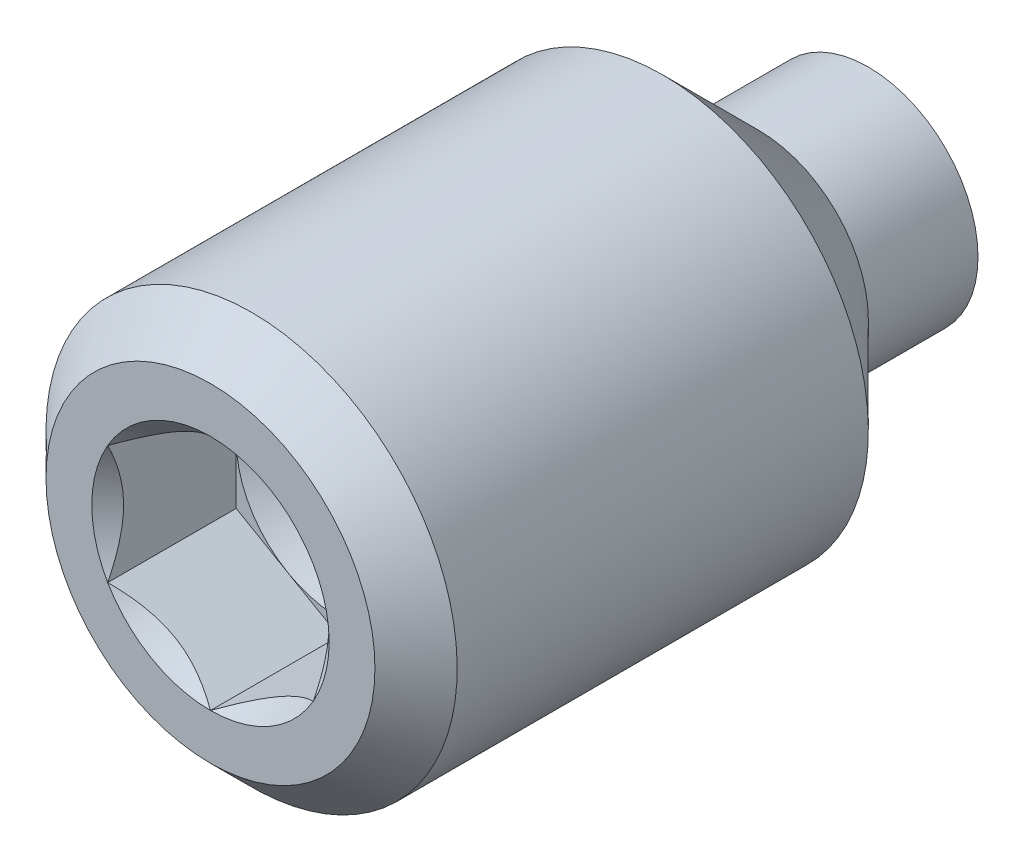
SolidWorks part; units mm, degrees
ref_plane "Front" through (0, 0, 0) normal (0, 0, 1) x (1, 0, 0)
ref_plane "Top" through (0, 0, 0) normal (0, 1, 0) x (1, 0, 0)
ref_plane "Right" through (0, 0, 0) normal (1, 0, 0) x (0, 0, -1)
sketch "Sketch22" plane through (0, 0, 0) normal (1, 0, 0) x (0, 0, -1)
  line L0 (-2.4, 0) -> (-2.4, 1.2)
  line L1 (-2.4, 1.2) -> (-2.1, 1.5)
  line L2 (-2.1, 1.5) -> (0.9, 1.5)
  line L3 (0.9, 1.5) -> (1.6, 0.8)
  line L5 (2.4, 0) -> (-2.4, 0)
  line L6 (2.4, 0) -> (1.6, 0) construction
  line L7 (1.6, 0) -> (1.6, 0.8) construction
  line L9 (-2.1, -1.5) -> (0.9, -1.5) construction
  line L10 (1.6, 0.8) -> (2.4, 0.8)
  line L11 (2.4, 0.8) -> (2.4, 0)
  line L12 (2.4, 0.8) -> (2.4, -0.8) construction
  dimension "Screw Dia" = 3
  dimension "Length" = 4
  dimension "D3" = 45
  dimension "D6" = 45
  dimension "D7" = 2.4
  dimension "A" = 1.6
  dimension "B" = 0.8
revolve "Revolve1" add sketch "Sketch22" angle 360 about L6
ref_plane "Plane2" through (0, 0, -1.6) normal (0, 0, 1) x (1, 0, 0)
sketch "Sketch27" plane through (0, 0, -1.6) normal (0, 0, 1) x (1, 0, 0)
  circle A0 centre (0, 0) radius 1.5
curve "Helix/Spiral1" pitch 0.5 height 4.5 turns 9
sketch "Sketch6" plane through (0, 0, 0) normal (1, 0, 0) x (0, 0, -1)
  line L0 (1.6938, 1.3376) -> (1.9438, 1.3376) construction
  line L3 (-2.1, 1.5) -> (0.9, 1.5) construction
  line L4 (1.85, 1.1752) -> (1.7875, 1.1752)
  line L5 (1.7875, 1.1752) -> (1.6, 1.5)
  line L6 (1.85, 1.1752) -> (2.0375, 1.5)
  line L7 (2.0375, 1.5) -> (1.6, 1.5)
  dimension "D1" = 0.25
  dimension "D2" = 0.0625
  dimension "D3" = 60
sweep "Cut-Sweep1" [suppressed] cut profiles "Sketch6" path "Helix/Spiral1"
sketch "Sketch30" plane through (0, 0, 2.4) normal (0, 0, 1) x (1, 0, 0)
  line L1 (0.75, -0.433) -> (0.75, 0.433)
  line L2 (0.75, 0.433) -> (0, 0.866)
  line L3 (0, 0.866) -> (-0.75, 0.433)
  line L4 (-0.75, 0.433) -> (-0.75, -0.433)
  line L5 (-0.75, -0.433) -> (0, -0.866)
  line L6 (0, -0.866) -> (0.75, -0.433)
  circle A0 centre (0, 0) radius 0.75 construction
  dimension "hex" = 1.5
extrude "Cut-Extrude1" cut sketch "Sketch30" against normal blind 0.9375
sketch "Sketch31" plane through (0, 0, 2.4) normal (0, 0, 1) x (1, 0, 0)
  circle A0 centre (0, 0) radius 0.866
extrude "Cut-Extrude2" cut sketch "Sketch31" against normal through all draft 45
sketch "Sketch32" plane through (0, 0, 1.4625) normal (0, 0, 1) x (1, 0, 0)
  circle A0 centre (0, 0) radius 0.75 construction
  circle A1 centre (0, 0) radius 0.75
extrude "Cut-Extrude3" cut sketch "Sketch32" against normal through all draft 60
sketch "Sketch29" plane through (0, 0, 0) normal (1, 0, 0) x (0, 0, -1)
  line L2 (-2.1, -1.5) -> (0.9, -1.5) construction
  point P1 (-2.4, 1.5)
  point P2 (1.6, 0.8)
  point P3 (2.4, 0.8)
  point P4 (2.4, -0.8)
  point P5 (2.4, -1.5)
  point P6 (-0.6, -1.5)
  point P7 (2.4, 1.5)
  dimension "D1" = 1.5
sketch "Sketch33" plane through (0, 0, 2.4) normal (0, 0, 1) x (1, 0, 0)
  circle A0 centre (0, 0) radius 1.5
equation "\"D7@Sketch22\"=\"Screw Dia@Sketch22\"*.8"
equation "\"D3@Helix/Spiral1\" = \"Length@Sketch22\" + \"D4@Helix/Spiral1\""
equation "\"D2@Sketch6\" = \"D4@Helix/Spiral1\" * .125"
equation "\"D1@Sketch6\" = \"D4@Helix/Spiral1\" * .5"
equation "\"D1@Sketch29\" = \"D4@Helix/Spiral1\" * 3"
equation "\"D1@Cut-Extrude1\" = \"hex@Sketch30\" * .625"
